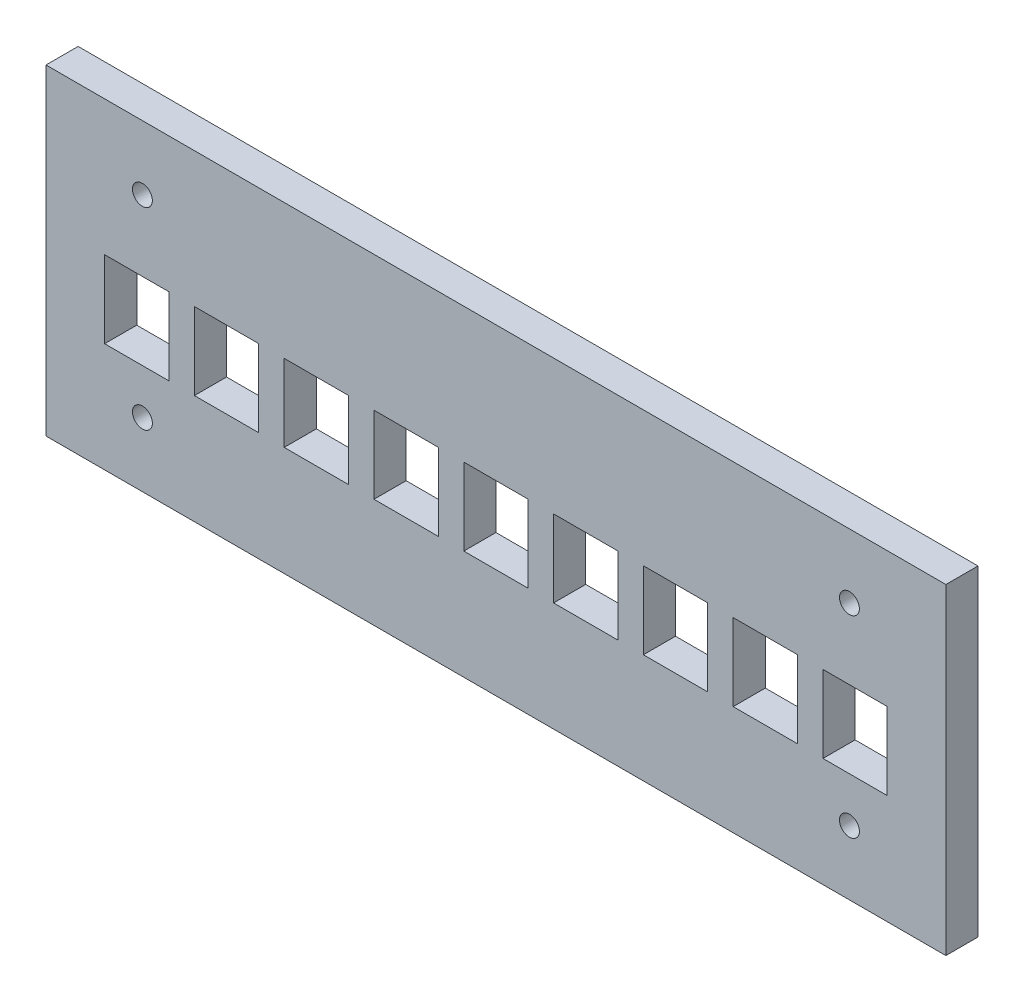
SolidWorks part; units mm, degrees
ref_plane "Plan de face" through (0, 0, 0) normal (0, 0, 1) x (1, 0, 0)
ref_plane "Plan de dessus" through (0, 0, 0) normal (0, 1, 0) x (1, 0, 0)
ref_plane "Plan de droite" through (0, 0, 0) normal (1, 0, 0) x (0, 0, -1)
sketch "Esquisse1" plane through (0, 0, 0) normal (0, 0, 1) x (1, 0, 0)
  line L0 (8.97, -8) -> (8.97, 4)
  line L5 (-70, -25) -> (70, -25)
  line L6 (-70, -25) -> (-70, 25)
  line L7 (-70, 25) -> (70, 25)
  line L8 (70, -25) -> (70, 25)
  line L9 (-70, -25) -> (70, 25) construction
  line L10 (-70, 25) -> (70, -25) construction
  line L11 (-5, -8) -> (5, -8)
  line L12 (-5, -8) -> (-5, 4)
  line L13 (-5, 4) -> (5, 4)
  line L14 (5, -8) -> (5, 4)
  line L15 (-5, -8) -> (5, 4) construction
  line L16 (-5, 4) -> (5, -8) construction
  line L17 (8.97, -8) -> (18.97, -8)
  line L18 (18.97, -8) -> (18.97, 4)
  line L19 (8.97, 4) -> (18.97, 4)
  line L20 (22.94, -8) -> (22.94, 4)
  line L21 (22.94, -8) -> (32.94, -8)
  line L22 (32.94, -8) -> (32.94, 4)
  line L23 (22.94, 4) -> (32.94, 4)
  line L24 (36.91, -8) -> (36.91, 4)
  line L25 (36.91, -8) -> (46.91, -8)
  line L26 (46.91, -8) -> (46.91, 4)
  line L27 (36.91, 4) -> (46.91, 4)
  line L28 (50.88, -8) -> (50.88, 4)
  line L29 (50.88, -8) -> (60.88, -8)
  line L30 (60.88, -8) -> (60.88, 4)
  line L31 (50.88, 4) -> (60.88, 4)
  line L32 (-5, -8) -> (8.97, -8) construction
  line L33 (-18.97, -8) -> (-18.97, 4)
  line L34 (-18.97, -8) -> (-8.97, -8)
  line L35 (-8.97, -8) -> (-8.97, 4)
  line L36 (-18.97, 4) -> (-8.97, 4)
  line L37 (-32.94, -8) -> (-32.94, 4)
  line L38 (-32.94, -8) -> (-22.94, -8)
  line L39 (-22.94, -8) -> (-22.94, 4)
  line L40 (-32.94, 4) -> (-22.94, 4)
  line L41 (-46.91, -8) -> (-46.91, 4)
  line L42 (-46.91, -8) -> (-36.91, -8)
  line L43 (-36.91, -8) -> (-36.91, 4)
  line L44 (-46.91, 4) -> (-36.91, 4)
  line L45 (-60.88, -8) -> (-60.88, 4)
  line L46 (-60.88, -8) -> (-50.88, -8)
  line L47 (-50.88, -8) -> (-50.88, 4)
  line L48 (-60.88, 4) -> (-50.88, 4)
  line L49 (-5, -8) -> (-18.97, -8) construction
  line L50 (0, 0) -> (0, 7.7631) construction
  line L51 (0, 0) -> (6.8675, 0) construction
  line L52 (0, -2) -> (0, 0) construction
  circle A0 centre (-55, -15) radius 1.55
  circle A1 centre (-55, 15) radius 1.55
  circle A2 centre (55, -15) radius 1.55
  circle A3 centre (55, 15) radius 1.55
  point P0 (0, 0)
  point P5 (0, 7.7631)
  point P8 (6.8675, 0)
  dimension "D9" = 3.1
  dimension "D1" = 140
  dimension "D2" = 50
  dimension "D3" = 10
  dimension "D4" = 12
  dimension "D6" = 13.97
  dimension "D8" = 13.97
  dimension "D10" = 15
  dimension "D11" = 10
  dimension "D12" = 23
  dimension "D5" = 5
  dimension "D7" = 5
extrude "Boss.-Extru.1" add sketch "Esquisse1" against normal blind 5
